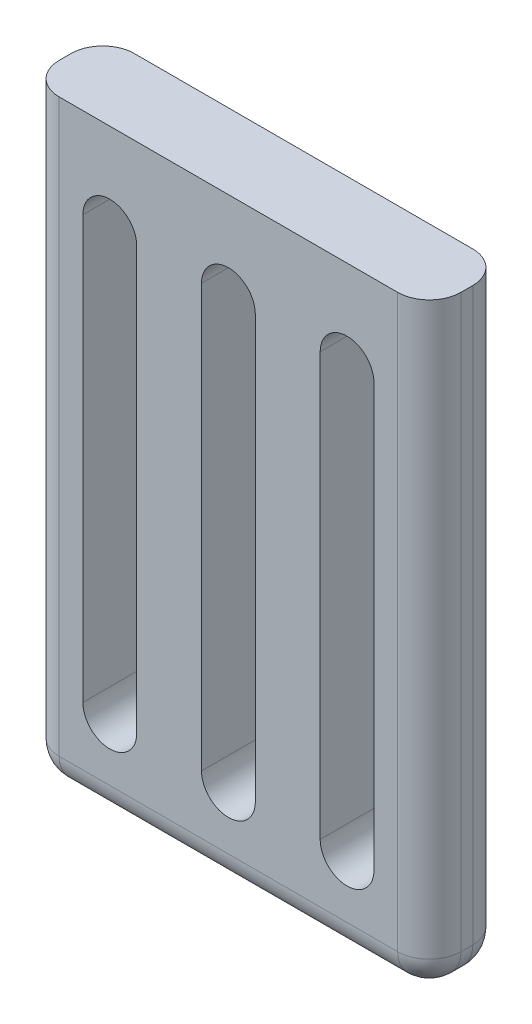
SolidWorks part; units mm, degrees
ref_plane "Front Plane" through (0, 0, 0) normal (0, 0, 1) x (1, 0, 0)
ref_plane "Top Plane" through (0, 0, 0) normal (0, 1, 0) x (1, 0, 0)
ref_plane "Right Plane" through (0, 0, 0) normal (1, 0, 0) x (0, 0, -1)
sketch "Sketch1" plane through (0, 0, 0) normal (0, 0, 1) x (1, 0, 0)
  line L1 (-12.7, 19.05) -> (12.7, 19.05)
  line L2 (-12.7, 19.05) -> (-12.7, -19.05)
  line L3 (-12.7, -19.05) -> (12.7, -19.05)
  line L4 (12.7, 19.05) -> (12.7, -19.05)
  line L5 (-12.7, 19.05) -> (12.7, -19.05) construction
  line L6 (-12.7, -19.05) -> (12.7, 19.05) construction
  point P0 (0, 0)
  dimension "D1" = 25.4
  dimension "D2" = 38.1
extrude "Boss-Extrude1" add sketch "Sketch1" along normal blind 4.75
sketch "Sketch2" plane through (0, 0, 4.75) normal (0, 0, 1) x (1, 0, 0)
  line L0 (0, -19.05) -> (0, 19.05) construction
  line L1 (12.7, 19.05) -> (-12.7, 19.05) construction
  line L2 (-7.5, 0) -> (7.5, 0) construction
  line L3 (9.2, 15.05) -> (5.8, 15.05)
  line L4 (-9.2, -15.05) -> (-5.8, -15.05)
  line L5 (-9.2, -15.05) -> (-9.2, 15.05)
  line L6 (-9.2, 15.05) -> (-5.8, 15.05)
  line L7 (-5.8, -15.05) -> (-5.8, 15.05)
  line L8 (-9.2, -15.05) -> (-5.8, 15.05) construction
  line L9 (-9.2, 15.05) -> (-5.8, -15.05) construction
  line L10 (5.8, -15.05) -> (5.8, 15.05)
  line L11 (9.2, -15.05) -> (5.8, -15.05)
  line L12 (9.2, -15.05) -> (9.2, 15.05)
  line L14 (-1.7, 15.05) -> (1.7, 15.05)
  line L15 (-1.7, 15.05) -> (-1.7, -15.05)
  line L16 (-1.7, -15.05) -> (1.7, -15.05)
  line L17 (1.7, 15.05) -> (1.7, -15.05)
  line L18 (-1.7, 15.05) -> (1.7, -15.05) construction
  line L19 (-1.7, -15.05) -> (1.7, 15.05) construction
  point P3 (0, 0)
  point P6 (0, 0)
  point P10 (0, 0)
  dimension "D1" = 15
  dimension "D2" = 3.4
  dimension "D3" = 30.1
  dimension "D4" = 3.4
  dimension "D5" = 30.1
extrude "Cut-Extrude1" cut sketch "Sketch2" against normal through all
fillet "Fillet1" 2 edges at (-9.2, 15.05, 2.375) (-5.8, 15.05, 2.375) type full round first side face at (-9.2, 0, 2.375) second side face at (-5.8, 0, 2.375) middle face at (-7.5, 15.05, 2.375)
fillet "Fillet2" 2 edges at (-9.2, -15.05, 2.375) (-5.8, -15.05, 2.375) type full round first side face at (-9.2, -0.85, 2.375) second side face at (-5.8, -0.85, 2.375) middle face at (-7.5, -15.05, 2.375)
fillet "Fillet3" 2 edges at (5.8, 15.05, 2.375) (9.2, 15.05, 2.375) type full round first side face at (5.8, 0, 2.375) second side face at (9.2, 0, 2.375) middle face at (7.5, 15.05, 2.375)
fillet "Fillet4" 2 edges at (5.8, -15.05, 2.375) (9.2, -15.05, 2.375) type full round first side face at (5.8, -0.85, 2.375) second side face at (9.2, -0.85, 2.375) middle face at (7.5, -15.05, 2.375)
fillet "Fillet5" radius 2 8 edges at (12.7, 0, 0) (12.7, 0, 4.75) (-12.7, 0, 0) (-12.7, 0, 4.75) (0, -19.05, 0) (0, -19.05, 4.75) (12.7, -19.05, 2.375) (-12.7, -19.05, 2.375)
sketch "Sketch3" plane through (0, 19.05, 0) normal (0, 1, 0) x (1, 0, 0)
  line L0 (0, 0) -> (0, -4.75) construction
  line L1 (10.7, -4.75) -> (-10.7, -4.75) construction
  circle A0 centre (0, -2.375) radius 1.0065
fillet "Fillet6" 2 edges at (-1.7, 15.05, 2.375) (1.7, 15.05, 2.375) type full round first side face at (-1.7, 0, 2.375) second side face at (1.7, 0, 2.375) middle face at (0, 15.05, 2.375)
fillet "Fillet7" 2 edges at (1.7, -15.05, 2.375) (-1.7, -15.05, 2.375) type full round first side face at (1.7, -0.85, 2.375) second side face at (-1.7, -0.85, 2.375) middle face at (0, -15.05, 2.375)
